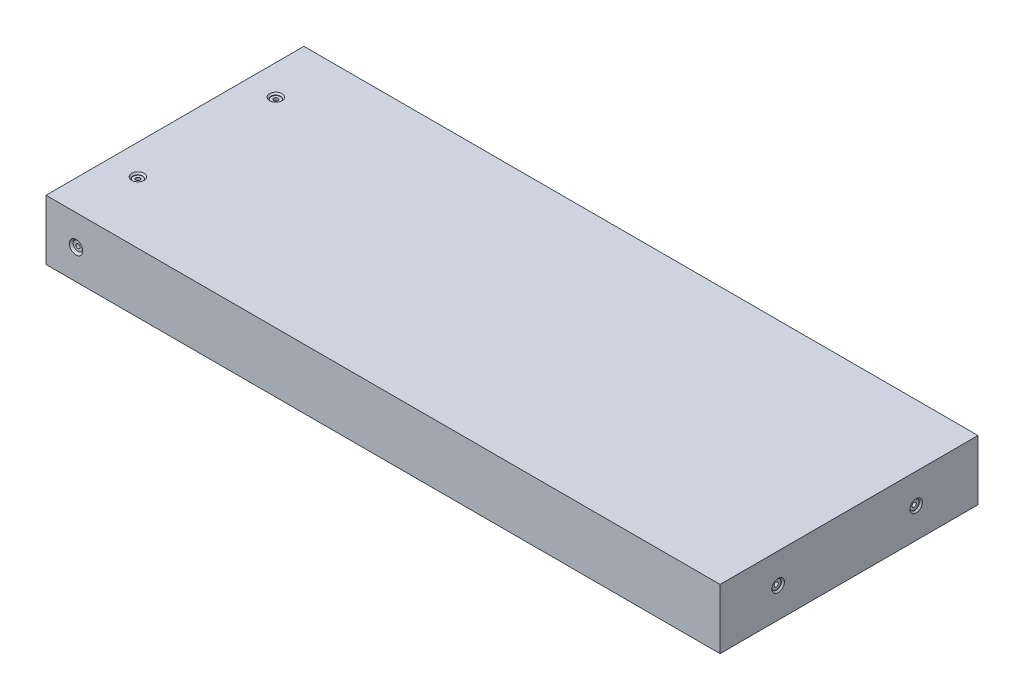
SolidWorks part; units mm, degrees
ref_plane "Front Plane" through (0, 0, 0) normal (0, 0, 1) x (1, 0, 0)
ref_plane "Top Plane" through (0, 0, 0) normal (0, 1, 0) x (1, 0, 0)
ref_plane "Right Plane" through (0, 0, 0) normal (1, 0, 0) x (0, 0, -1)
sketch "Sketch1" plane through (0, 0, 0) normal (0, 1, 0) x (1, 0, 0)
  line L1 (-142.7, 54.6) -> (142.7, 54.6)
  line L2 (-142.7, 54.6) -> (-142.7, -54.6)
  line L3 (-142.7, -54.6) -> (142.7, -54.6)
  line L4 (142.7, 54.6) -> (142.7, -54.6)
  line L5 (-142.7, 54.6) -> (142.7, -54.6) construction
  line L6 (-142.7, -54.6) -> (142.7, 54.6) construction
  point P0 (0, 0)
  dimension "D1" = 109.2
  dimension "D2" = 285.4
extrude "Boss-Extrude1" add sketch "Sketch1" along normal blind 25.4
hole_wizard "CBORE for #0 Binding Head Machine Screw1" positions "Sketch2" profile "Sketch3" counterbore size "#0" standard "ANSI Inch"
sketch "Sketch2" plane through (0, 0, 54.6) normal (0, 0, 1) x (1, 0, 0)
  line L0 (-142.7, 25.4) -> (-142.7, 0) construction
  line L1 (-142.7, 25.4) -> (142.7, 25.4) construction
  point P0 (-130, 12.7)
  dimension "D1" = 12.7
  dimension "D2" = 12.7
sketch "Sketch3" plane through (-130, 12.7, 54.6) normal (1, 0, 0) x (0, -1, 0)
  line L0 (0, 0) -> (0, 30.5342)
  line L1 (0, 30.5342) -> (0.889, 30)
  line L2 (0.889, 30) -> (0.889, 0.8128)
  line L3 (0.889, 0.8128) -> (1.985, 0.8128)
  line L5 (1.985, 0.8128) -> (1.985, 0.8725)
  line L6 (1.985, 0.8725) -> (2.8575, 0)
  line L7 (2.8575, 0) -> (0, 0)
  line L8 (-1.985, 0.8725) -> (-2.8575, 0) construction
  line L10 (0, 30.5342) -> (-0.889, 30) construction
  line L11 (0, -6.35) -> (0, 107.95) construction
  dimension "Hole Dia." = 1.778
  dimension "Hole Depth" = 30
  dimension "C'Bore Dia." = 3.97
  dimension "C'Bore Depth" = 0.8128
  dimension "Near C'Sink Dia." = 5.715
  dimension "Near C'Sink Angle" = 90
  dimension "Drill Angle" = 118
mirror "Mirror1" about plane through (0, 0, 0) normal (0, 0, 1) of "CBORE for #0 Binding Head Machine Screw1"
hole_wizard "CBORE for #0 Binding Head Machine Screw2" positions "Sketch4" profile "Sketch5" counterbore size "#0" standard "ANSI Inch"
sketch "Sketch4" plane through (142.7, 0, 0) normal (1, 0, 0) x (0, 0, -1)
  line L0 (-54.6, 25.4) -> (-54.6, 0) construction
  line L2 (-54.6, 25.4) -> (54.6, 25.4) construction
  point P0 (-30, 12.7)
  point P2 (28.4, 12.7)
  dimension "D1" = 58.4
  dimension "D2" = 24.6
  dimension "D4" = 12.7
sketch "Sketch5" plane through (142.7, 12.7, 30) normal (0, 1, 0) x (0, 0, -1)
  line L0 (0, 0) -> (0, 30.5342)
  line L1 (0, 30.5342) -> (0.889, 30)
  line L2 (0.889, 30) -> (0.889, 0.8128)
  line L3 (0.889, 0.8128) -> (1.985, 0.8128)
  line L5 (1.985, 0.8128) -> (1.985, 0.635)
  line L6 (1.985, 0.635) -> (2.62, 0)
  line L7 (2.62, 0) -> (0, 0)
  line L8 (-1.985, 0.635) -> (-2.62, 0) construction
  line L10 (0, 30.5342) -> (-0.889, 30) construction
  line L11 (0, -6.35) -> (0, 107.95) construction
  dimension "Hole Dia." = 1.778
  dimension "Hole Depth" = 30
  dimension "C'Bore Dia." = 3.97
  dimension "C'Bore Depth" = 0.8128
  dimension "Near C'Sink Dia." = 5.24
  dimension "Near C'Sink Angle" = 90
  dimension "Drill Angle" = 118
hole_wizard "CBORE for #0 Binding Head Machine Screw3" positions "Sketch6" profile "Sketch7" counterbore size "#0" standard "ANSI Inch"
sketch "Sketch6" plane through (0, 25.4, 0) normal (0, 1, 0) x (1, 0, 0)
  line L0 (-142.7, 54.6) -> (-142.7, -54.6) construction
  line L1 (142.7, 54.6) -> (-142.7, 54.6) construction
  point P0 (-130, 30)
  point P2 (-130, -28.4)
  point P15 (0, 0)
  dimension "D1" = 12.7
  dimension "D2" = 58.4
  dimension "D3" = 24.6
  dimension "D4" = 12.7
sketch "Sketch7" plane through (-130, 25.4, -30) normal (1, 0, 0) x (0, 0, 1)
  line L0 (0, 0) -> (0, 30.5342)
  line L1 (0, 30.5342) -> (0.889, 30)
  line L2 (0.889, 30) -> (0.889, 0.8128)
  line L3 (0.889, 0.8128) -> (1.985, 0.8128)
  line L5 (1.985, 0.8128) -> (1.985, 0.635)
  line L6 (1.985, 0.635) -> (2.62, 0)
  line L7 (2.62, 0) -> (0, 0)
  line L8 (-1.985, 0.635) -> (-2.62, 0) construction
  line L10 (0, 30.5342) -> (-0.889, 30) construction
  line L11 (0, -6.35) -> (0, 107.95) construction
  dimension "Hole Dia." = 1.778
  dimension "Hole Depth" = 30
  dimension "C'Bore Dia." = 3.97
  dimension "C'Bore Depth" = 0.8128
  dimension "Near C'Sink Dia." = 5.24
  dimension "Near C'Sink Angle" = 90
  dimension "Drill Angle" = 118
